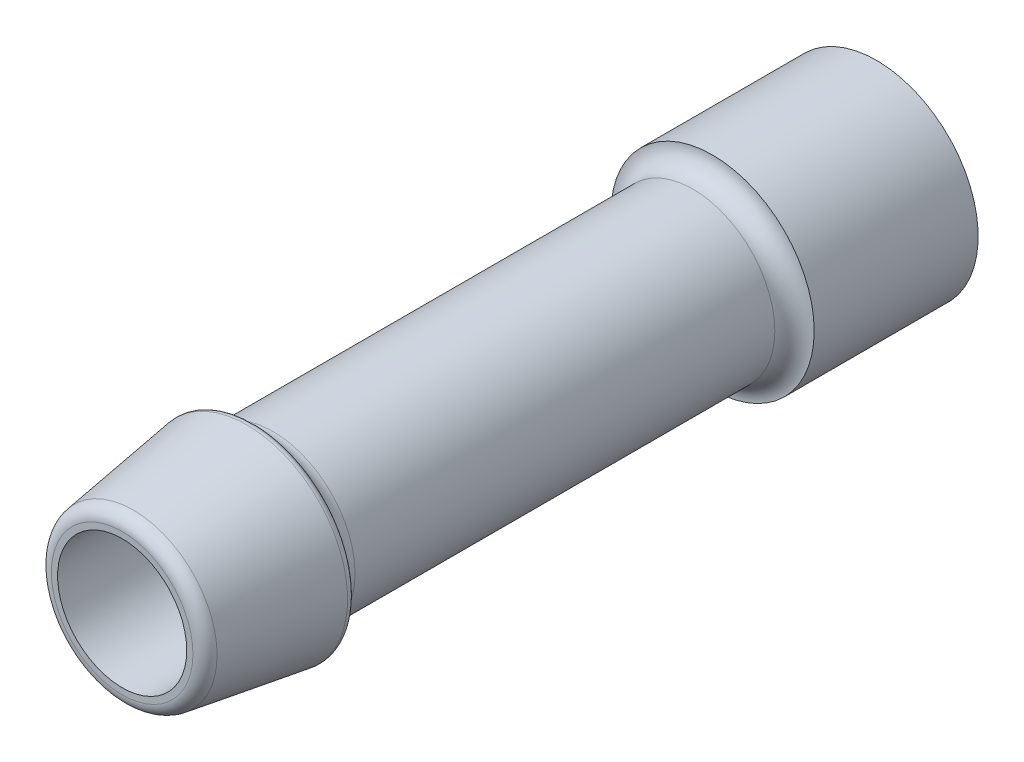
SolidWorks part; units mm, degrees
material "Custom Plastic"
ref_plane "X-Y Datum" through (0, 0, 0) normal (0, 0, 1) x (1, 0, 0)
ref_plane "X-Z Datum" through (0, 0, 0) normal (0, 1, 0) x (1, 0, 0)
ref_plane "Y-Z Datum" through (0, 0, 0) normal (1, 0, 0) x (0, 0, -1)
sketch "Sketch1" plane through (0, 0, 0) normal (0, 0, 1) x (1, 0, 0)
  circle A0 centre (0, 0) radius 3.937
  dimension "D1" = 7.874
extrude "Boss-Extrude1" add sketch "Sketch1" along normal blind 29.21
sketch3d "3DSketch1"
  line L0 (0, 0, 29.21) -> (0, 0, 0)
  line L1 (0, 0, 29.21) -> (0, 0, 0) construction
sketch "Sketch2" plane through (0, 0, 29.21) normal (0, 0, 1) x (1, 0, 0)
  circle A0 centre (0, 0) radius 2.5
  dimension "D1" = 5
sweep "Cut-Sweep1" cut profiles "Sketch2" path "3DSketch1"
sketch "Sketch3" plane through (0, 0, 29.21) normal (0, 0, 1) x (1, 0, 0)
  circle A0 centre (0, 0) radius 3.175
  circle A1 centre (0, 0) radius 5.08
extrude "Cut-Extrude1" cut sketch "Sketch3" against normal blind 17.78 from offset 5.08 offset against normal yes
fillet "Fillet1" radius 0.762 1 edges at (3.175, 0, 6.35)
fillet "Fillet2" radius 0.762 1 edges at (3.175, 0, 24.13)
chamfer "Chamfer1" distance 5.08 angle 8.5 1 edges at (3.937, 0, 29.21) first distance on face at (3.937, 0, 24.13)
fillet "Fillet3" radius 0.254 1 edges at (3.937, 0, 24.13)
fillet "Fillet4" radius 0.508 1 edges at (3.1778, 0, 29.21)
